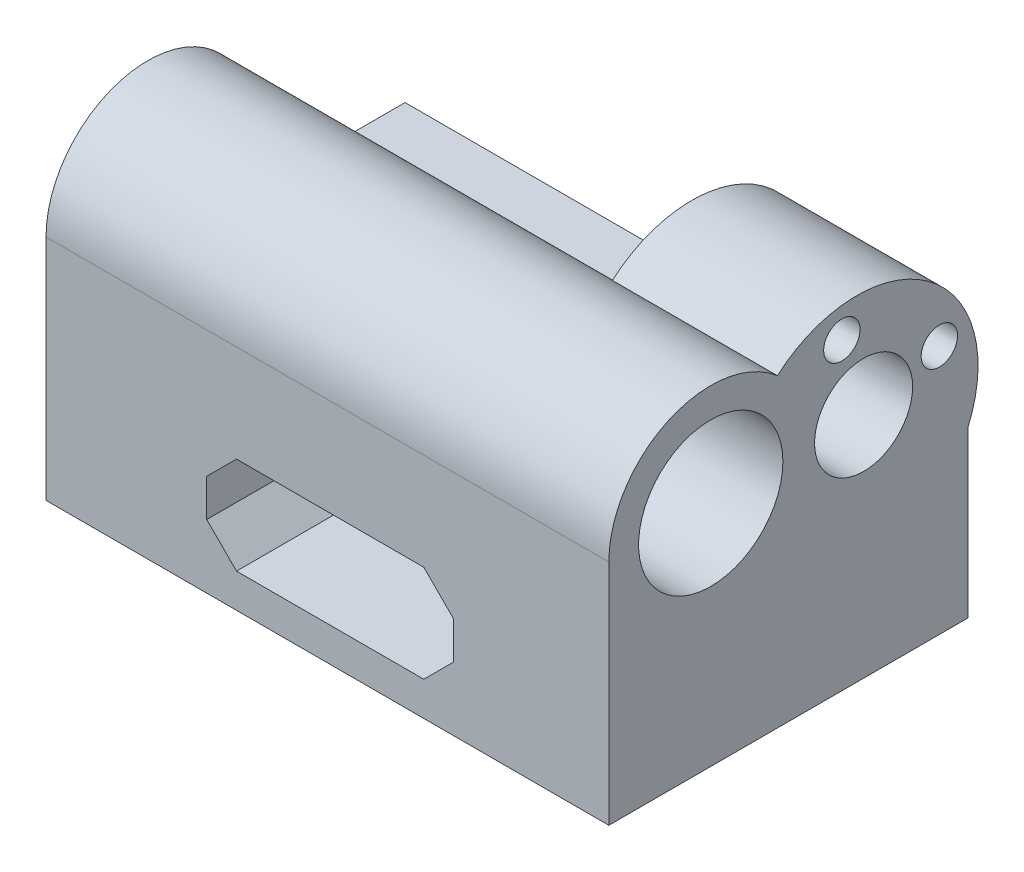
SolidWorks part; units mm, degrees
ref_plane "Front Plane" through (0, 0, 0) normal (0, 0, 1) x (1, 0, 0)
ref_plane "Top Plane" through (0, 0, 0) normal (0, 1, 0) x (1, 0, 0)
ref_plane "Right Plane" through (0, 0, 0) normal (1, 0, 0) x (0, 0, -1)
sketch "Sketch2" plane through (0, 0, 0) normal (0, 1, 0) x (1, 0, 0)
  line L1 (-29, -18.5) -> (29, -18.5)
  line L2 (-29, -18.5) -> (-29, 18.5)
  line L3 (-29, 18.5) -> (29, 18.5)
  line L4 (29, -18.5) -> (29, 18.5)
  line L5 (-29, -18.5) -> (29, 18.5) construction
  line L6 (-29, 18.5) -> (29, -18.5) construction
  point P0 (0, 0)
  dimension "D1" = 58
  dimension "D2" = 37
extrude "Boss-Extrude1" add sketch "Sketch2" along normal blind 17
sketch "Sketch3" plane through (29, 0, 0) normal (1, 0, 0) x (0, 0, -1)
  line L0 (-18.5, 0) -> (18.5, 0) construction
  line L1 (-18.5, 23.5) -> (-18.5, 17)
  line L2 (-18.5, 17) -> (-18.5, 0) construction
  line L5 (2.5, 23.5) -> (2.5, 17)
  line L6 (-18.5, 17) -> (18.5, 17) construction
  line L7 (-18.5, 17) -> (2.5, 17)
  arc A0 (2.5, 23.5) -> (-18.5, 23.5) centre (-8, 23.5) ccw
  dimension "D2" = 21
  dimension "D4" = 23.5
  dimension "D5" = 10.5
extrude "Boss-Extrude2" add sketch "Sketch3" against normal up to surface (58 mm away) up to face at (-29, 8.5, 0)
sketch "Sketch4" plane through (29, 0, 0) normal (1, 0, 0) x (0, 0, -1)
  line L1 (-18.5, 0) -> (18.5, 0) construction
  circle A0 centre (7.0436, 22) radius 12.5
  dimension "D1" = 25
  dimension "D2" = 22
extrude "Boss-Extrude3" add sketch "Sketch4" against normal blind 17
sketch "Sketch5" plane through (0, 0, -18.5) normal (0, 0, -1) x (-1, 0, 0)
  line L0 (-13, 6.57) -> (-13, 10.427)
  line L1 (-13, 10.427) -> (-9.93, 13.497)
  line L2 (-9.93, 13.497) -> (9.37, 13.497)
  line L3 (9.37, 13.497) -> (12.44, 10.427)
  line L4 (12.44, 10.427) -> (12.44, 6.57)
  line L5 (12.44, 6.57) -> (9.37, 3.5)
  line L6 (9.37, 3.5) -> (-9.93, 3.5)
  line L7 (-9.93, 3.5) -> (-13, 6.57)
  line L8 (-29, 0) -> (29, 0) construction
  line L9 (-29, 17) -> (-29, 0) construction
  dimension "D1" = 3.857
  dimension "D2" = 3.857
  dimension "D3" = 135
  dimension "D4" = 135
  dimension "D5" = 3.07
  dimension "D6" = 3.07
  dimension "D7" = 3.07
  dimension "D8" = 3.07
  dimension "D9" = 19.3
  dimension "D10" = 3.5
  dimension "D11" = 16
extrude "Cut-Extrude1" cut sketch "Sketch5" against normal through all
sketch "Sketch6" plane through (0, 0, -18.5) normal (0, 0, -1) x (-1, 0, 0)
  line L0 (-29, 0) -> (29, 0) construction
  line L1 (-29, 17) -> (-29, 0) construction
  circle A0 centre (-23, 8.5) radius 4.076
  circle A1 centre (22, 8.5) radius 4.076
  dimension "D5" = 8.152
  dimension "D6" = 8.152
  dimension "D1" = 8.5
  dimension "D2" = 8.5
  dimension "D3" = 6
  dimension "D4" = 51
extrude "Cut-Extrude2" cut sketch "Sketch6" against normal blind 23
sketch "Sketch7" plane through (29, 0, 0) normal (1, 0, 0) x (0, 0, -1)
  line L0 (-18.5, 23.5) -> (-18.5, 0) construction
  line L1 (-18.5, 0) -> (18.5, 0) construction
  circle A0 centre (-8, 23.5) radius 7.4365
  circle A1 centre (7.7501, 23.5) radius 5.05
  dimension "D1" = 10.1
  dimension "D2" = 14.873
  dimension "D3" = 26.2501
  dimension "D4" = 23.5
extrude "Cut-Extrude3" cut sketch "Sketch7" against normal through all
sketch "Sketch8" plane through (29, 0, 0) normal (1, 0, 0) x (0, 0, -1)
  line L0 (7.7501, 23.5) -> (5.5097, 31.31) construction
  line L3 (7.7501, 23.5) -> (15.5601, 25.7405) construction
  line L4 (5.5097, 31.31) -> (6.0267, 29.5077) construction
  line L7 (15.5601, 25.7405) -> (13.7578, 25.2235) construction
  circle A1 centre (5.5097, 31.31) radius 1.875
  circle A2 centre (15.5601, 25.7405) radius 1.875
  dimension "D1" = 3.75
  dimension "D2" = 6.25
  dimension "D3" = 3.75
  dimension "D7" = 6.25
extrude "Cut-Extrude4" cut sketch "Sketch8" against normal through all
sketch "Sketch9" plane through (12, 0, 0) normal (-1, 0, 0) x (0, 0, 1)
  circle A0 centre (-5.5097, 31.31) radius 2.75
  circle A1 centre (-15.5601, 25.7405) radius 2.75
  dimension "D1" = 5.5
  dimension "D2" = 5.5
